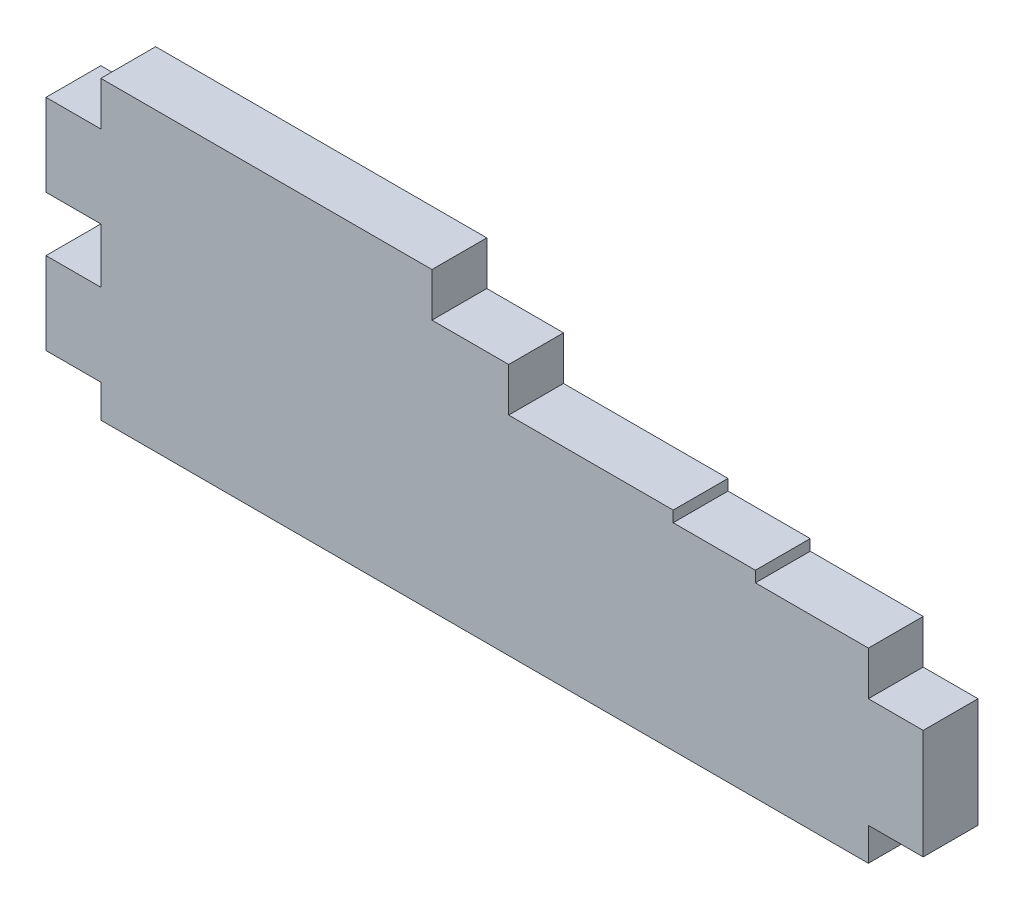
SolidWorks part; units mm, degrees
ref_plane "Plan de face" through (0, 0, 0) normal (0, 0, 1) x (1, 0, 0)
ref_plane "Plan de dessus" through (0, 0, 0) normal (0, 1, 0) x (1, 0, 0)
ref_plane "Plan de droite" through (0, 0, 0) normal (1, 0, 0) x (0, 0, -1)
sketch "Esquisse1" plane through (0, 0, 0) normal (0, 0, 1) x (1, 0, 0)
  line L0 (15.1, 0) -> (15.1, 24) construction
  line L1 (0, 0) -> (-5, 0)
  line L2 (0, 7.5) -> (0, 12.5)
  line L3 (0, 24) -> (30.2, 24)
  line L4 (30.2, 20) -> (30.2, 24)
  line L5 (0, 0) -> (0, -3)
  line L6 (-5, 20) -> (0, 20)
  line L8 (0, 12.5) -> (-5, 12.5)
  line L9 (-5, 20) -> (-5, 12.5)
  line L10 (0, 0) -> (-5, 0)
  line L12 (0, 7.5) -> (-5, 7.5)
  line L13 (-5, 0) -> (-5, 7.5)
  line L15 (70, 10) -> (70, 14)
  line L16 (70, 0) -> (75, 0)
  line L17 (52.2, 15) -> (52.2, 16)
  line L18 (70, 10) -> (75, 10)
  line L19 (75, 0) -> (75, 10)
  line L22 (52.2, 15) -> (59.7, 15)
  line L23 (0, 20) -> (0, 24)
  line L24 (59.7, 15) -> (59.7, 14)
  line L25 (59.7, 14) -> (70, 14)
  line L27 (37.2, 16) -> (52.2, 16)
  line L28 (70, 0) -> (70, -3)
  line L29 (70, -3) -> (0, -3)
  line L34 (30.2, 20) -> (37.2, 20)
  line L37 (37.2, 20) -> (37.2, 16)
  dimension "D2" = 24
  dimension "D3" = 75
  dimension "D4" = 7.5
  dimension "D5" = 5
  dimension "D7" = 18
  dimension "D8" = 3
  dimension "D9" = 30.2
  dimension "D10" = 7.5
  dimension "D11" = 4
  dimension "D12" = 15
  dimension "D13" = 10
  dimension "D14" = 3
  dimension "D15" = 5
  dimension "D16" = 4
  dimension "D17" = 7
  dimension "D18" = 17
extrude "Boss.-Extru.1" add sketch "Esquisse1" along normal blind 5 contours L29 L28 L16 L19 L18 L15 L25 L24 L22 L17 L4 L3 L9 L8 L2 L12 L13 region at (31.1369, 8.5799, 0)
